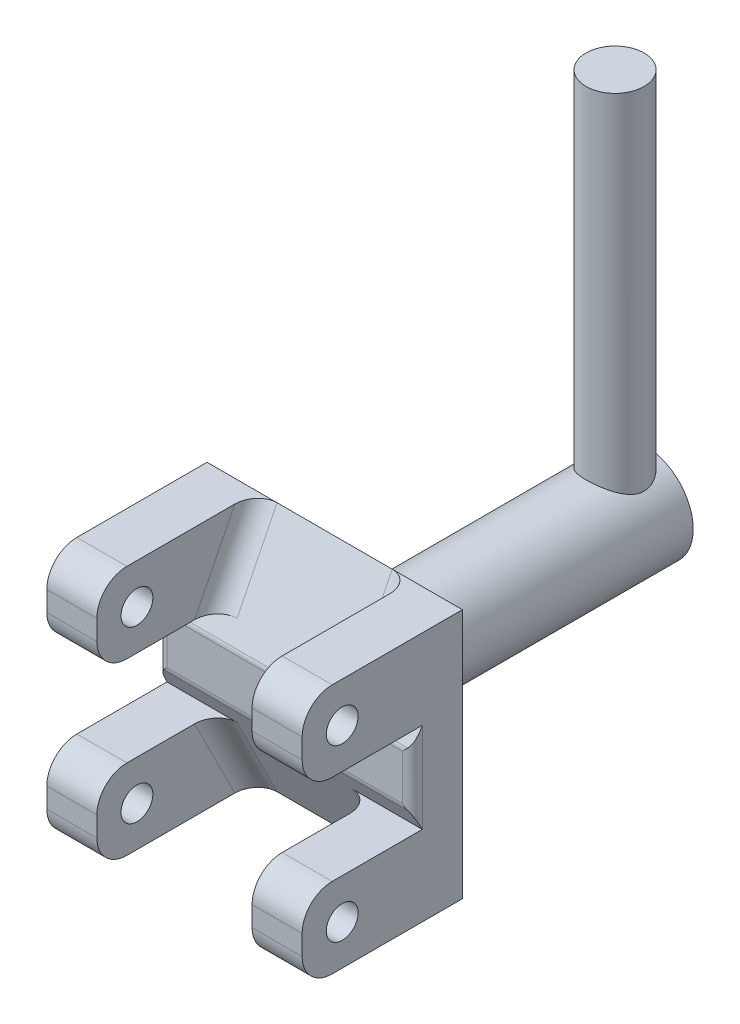
SolidWorks part; units mm, degrees
ref_plane "Plan de face" through (0, 0, 0) normal (0, 0, 1) x (1, 0, 0)
ref_plane "Plan de dessus" through (0, 0, 0) normal (0, 1, 0) x (1, 0, 0)
ref_plane "Plan de droite" through (0, 0, 0) normal (1, 0, 0) x (0, 0, -1)
ref_plane "Plan1" through (12.75, 0, 0) normal (1, 0, 0) x (0, 0, -1)
sketch "Esquisse1" plane through (12.75, 0, 0) normal (1, 0, 0) x (0, 0, -1)
  line L0 (-5, -2.5) -> (0, -12.5)
  line L1 (0, -12.5) -> (0, 12.5)
  line L2 (0, 12.5) -> (-5, 2.5)
  line L3 (-5, 2.5) -> (-5, -2.5)
extrude "Boss.-Extru.1" add sketch "Esquisse1" against normal blind 25.5
ref_plane "Plan2" through (-12.75, 0, 0) normal (-1, 0, 0) x (0, -1, 0)
sketch "Esquisse2" plane through (-12.75, 0, 0) normal (-1, 0, 0) x (0, -1, 0)
  line L0 (4.5, 16) -> (4.5, 4)
  line L1 (4.5, 4) -> (12.5, 0)
  line L2 (12.5, 0) -> (12.5, 16)
  line L3 (12.5, 16) -> (4.5, 16)
extrude "Boss.-Extru.2" add sketch "Esquisse2" against normal blind 5
sketch "Esquisse3" plane through (12.75, 0, 0) normal (1, 0, 0) x (0, 0, -1)
  line L0 (-16, -12.5) -> (0, -12.5)
  line L1 (0, -12.5) -> (-4, -4.5)
  line L2 (-4, -4.5) -> (-16, -4.5)
  line L3 (-16, -4.5) -> (-16, -12.5)
extrude "Boss.-Extru.3" add sketch "Esquisse3" against normal blind 5
sketch "Esquisse4" plane through (12.75, 0, 0) normal (1, 0, 0) x (0, 0, -1)
  line L0 (-16, 4.5) -> (-4, 4.5)
  line L1 (-4, 4.5) -> (0, 12.5)
  line L2 (0, 12.5) -> (-16, 12.5)
  line L3 (-16, 12.5) -> (-16, 4.5)
extrude "Boss.-Extru.4" add sketch "Esquisse4" against normal blind 5
sketch "Esquisse5" plane through (-12.75, 0, 0) normal (-1, 0, 0) x (0, -1, 0)
  line L0 (-4.5, 16) -> (-12.5, 16)
  line L1 (-12.5, 16) -> (-12.5, 0)
  line L2 (-12.5, 0) -> (-4.5, 4)
  line L3 (-4.5, 4) -> (-4.5, 16)
extrude "Boss.-Extru.5" add sketch "Esquisse5" against normal blind 5
sketch "Esquisse6" plane through (0, 0, 0) normal (0, 1, 0) x (1, 0, 0)
  line L0 (4.8, 31) -> (0, 31)
  line L1 (0, 31) -> (0, 0)
  line L2 (0, 0) -> (4.8, 0)
  line L3 (4.8, 0) -> (4.8, 31)
  line L4 (0, 31) -> (0, 0) construction
revolve "Révolution1" add sketch "Esquisse6" angle 360 about L4 reverse direction yes
ref_plane "Plan3" through (0.0098, 0, -28) normal (-0.0003, 0, 1) x (1, 0, 0.0003)
sketch "Esquisse7" plane through (0.0098, 0, -28) normal (-0.0003, 0, 1) x (1, 0, 0.0003)
  line L0 (-2.9098, 3.8249) -> (-0.0098, 3.8249)
  line L1 (-0.0098, 3.8249) -> (-0.0098, 38.8249)
  line L2 (-0.0098, 38.8249) -> (-2.9098, 38.8249)
  line L3 (-2.9098, 38.8249) -> (-2.9098, 3.8249)
  line L4 (-0.0098, 3.8249) -> (-0.0098, 38.8249) construction
  dimension "D1" = 35
revolve "Révolution2" add sketch "Esquisse7" angle 360 about L4 reverse direction yes
hole_wizard "Perçage1" positions "Esquisse9" profile "Esquisse8" legacy
sketch "Esquisse9" plane through (-12.75, 0, 0) normal (-1, 0, 0) x (0, 0, 1)
  point P0 (12, -8.5)
sketch "Esquisse8" plane through (-12.75, -8.5, 12) normal (0, 1, 0) x (0, 0, 1)
  line L0 (0, 0) -> (0, 5)
  line L1 (0, 5) -> (1.59, 5)
  line L2 (1.59, 5) -> (1.59, 0)
  line L3 (1.59, 0) -> (0, 0)
  line L4 (0, 110) -> (0, -10) construction
  dimension "Diamètre" = 3.18
  dimension "Profondeur" = 5
hole_wizard "Perçage2" positions "Esquisse11" profile "Esquisse10" legacy
sketch "Esquisse11" plane through (7.75, 0, 0) normal (-1, 0, 0) x (0, 0, 1)
  point P0 (12, -8.5)
sketch "Esquisse10" plane through (7.75, -8.5, 12) normal (0, 1, 0) x (0, 0, 1)
  line L0 (0, 0) -> (0, 5)
  line L1 (0, 5) -> (1.59, 5)
  line L2 (1.59, 5) -> (1.59, 0)
  line L3 (1.59, 0) -> (0, 0)
  line L4 (0, 110) -> (0, -10) construction
  dimension "Diamètre" = 3.18
  dimension "Profondeur" = 5
hole_wizard "Perçage3" positions "Esquisse13" profile "Esquisse12" legacy
sketch "Esquisse13" plane through (12.75, 0, 0) normal (1, 0, 0) x (0, 0, -1)
  point P0 (-12, 8.5)
sketch "Esquisse12" plane through (12.75, 8.5, 12) normal (0, 1, 0) x (0, 0, -1)
  line L0 (0, 0) -> (0, 5)
  line L1 (0, 5) -> (1.59, 5)
  line L2 (1.59, 5) -> (1.59, 0)
  line L3 (1.59, 0) -> (0, 0)
  line L4 (0, 110) -> (0, -10) construction
  dimension "Diamètre" = 3.18
  dimension "Profondeur" = 5
hole_wizard "Perçage4" positions "Esquisse15" profile "Esquisse14" legacy
sketch "Esquisse15" plane through (-7.75, 0, 0) normal (1, 0, 0) x (0, 0, -1)
  point P0 (-12, 8.5)
sketch "Esquisse14" plane through (-7.75, 8.5, 12) normal (0, 1, 0) x (0, 0, -1)
  line L0 (0, 0) -> (0, 5)
  line L1 (0, 5) -> (1.59, 5)
  line L2 (1.59, 5) -> (1.59, 0)
  line L3 (1.59, 0) -> (0, 0)
  line L4 (0, 110) -> (0, -10) construction
  dimension "Diamètre" = 3.18
  dimension "Profondeur" = 5
fillet "Congé1" radius 1 4 edges at (-12.75, 0, 5) (0, -2.5, 5) (0, 2.5, 5) (12.75, 0, 5)
fillet "Congé2" radius 2 5 edges at (4.8, 0, 0) (7.75, -8.5, 2) (7.75, 8.5, 2) (-7.75, 8.5, 2) (-7.75, -8.5, 2) tangent propagation no
fillet "Congé3" radius 3 8 edges at (10.25, 12.5, 16) (10.25, -4.5, 16) (10.25, -12.5, 16) (-10.25, -12.5, 16) (10.25, 4.5, 16) (-10.25, -4.5, 16) (-10.25, 4.5, 16) (-10.25, 12.5, 16) tangent propagation no
